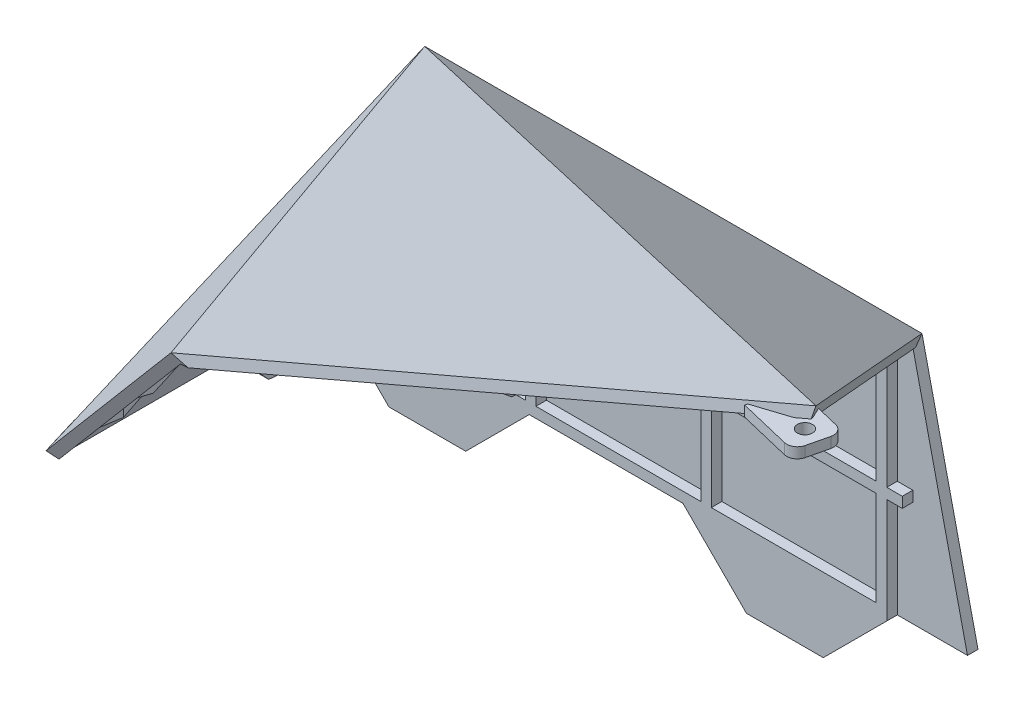
SolidWorks part; units mm, degrees
ref_plane "前视基准面" through (0, 0, 0) normal (0, 0, 1) x (1, 0, 0)
ref_plane "上视基准面" through (0, 0, 0) normal (0, 1, 0) x (1, 0, 0)
ref_plane "右视基准面" through (0, 0, 0) normal (1, 0, 0) x (0, 0, -1)
sketch "Sketch1" plane through (0, 0, 0) normal (0, 0, 1) x (1, 0, 0)
  line L0 (-295, -10) -> (-113.1586, -10)
  line L1 (-295, -10) -> (295, -10) construction
  line L2 (-113.1586, -10) -> (-129.1191, 60)
  line L3 (-129.1191, 60) -> (-270.8573, 60)
  line L4 (-270.8573, 60) -> (-295, -10)
  line L5 (-55, -10) -> (-295, -10) construction
  dimension "D1" = 70
extrude "Extrude1" add sketch "Sketch1" against normal blind 3
sketch "Sketch2" plane through (-260.5569, 89.8651, 0) normal (-0.9454, 0.326, 0) x (0, 0, 1)
  line L0 (0, -31.5915) -> (0, -105.6379)
  line L1 (0, -31.5915) -> (0, -105.6379) construction
  line L2 (0, -105.6379) -> (80.7874, -105.6379)
  line L5 (0, -31.5915) -> (80.7874, -105.6379)
extrude "Extrude2" add sketch "Sketch2" against normal blind 3
ref_plane "Plane1" through (0, 90, 0) normal (0, -1, 0) x (-1, 0, 0)
sketch "Sketch3" plane through (0, 90, 0) normal (0, -1, 0) x (-1, 0, 0)
  line L0 (201.3797, -153.6318) -> (201.3797, -124.7992) construction
  line L2 (226.9384, -143.7928) -> (224.0406, -143.7928) construction
  point P4 (201.3797, -138.7928)
  dimension "D1" = 5
ref_plane "Plane4" through (0, 120, 0) normal (0, 1, 0) x (1, 0, 0)
sketch "Sketch6" plane through (0, 120, 0) normal (0, 1, 0) x (1, 0, 0)
  point P0 (-66.3616, -89.9707)
ref_plane "Plane5" through (0, 43.7249, -28.2185) normal (0, 0.8402, -0.5422) x (1, 0, 0)
sketch "Sketch7" plane through (0, 43.7249, -28.2185) normal (0, 0.8402, -0.5422) x (1, 0, 0)
  line L0 (-66.3616, -140.6648) -> (-129.1191, -30.0142)
  line L1 (-129.1191, -30.0142) -> (-270.8573, -30.0142)
  line L2 (-270.8573, -30.0142) -> (-66.3616, -140.6648)
extrude "Extrude4" add sketch "Sketch7" against normal blind 3
ref_axis "Axis1" through (-270.8573, 60, -3) along (-0.2159, -0.626, 0.7493)
ref_plane "Plane6" through (-189.0801, 140.5222, 62.9169) normal (-0.7754, 0.5763, 0.258) x (0.214, -0.1446, 0.9661)
sketch "Sketch8" plane through (-189.0801, 140.5222, 62.9169) normal (-0.7754, 0.5763, 0.258) x (0.214, -0.1446, 0.9661)
  line L0 (77.9736, -48.7959) -> (-69.5404, -112.6077)
  line L1 (-69.5404, -112.6077) -> (16.3577, -184.1948)
  line L2 (16.3577, -184.1948) -> (77.9736, -48.7959)
extrude "Extrude5" add sketch "Sketch8" against normal blind 3
ref_plane "Plane7" through (-30.5316, 120.3261, -10.4979) normal (-0.2451, 0.9658, -0.0843) x (0.9695, 0.2441, -0.0213)
sketch "Sketch9" plane through (-30.5316, 120.3261, -10.4979) normal (-0.2451, 0.9658, -0.0843) x (0.9695, 0.2441, -0.0213)
  line L0 (-36.9571, -100.06) -> (-176.222, -146.0899)
  line L1 (-176.222, -146.0899) -> (-247.8849, -2.2263)
  line L2 (-247.8849, -2.2263) -> (-36.9571, -100.06)
extrude "Extrude6" add sketch "Sketch9" against normal blind 3
sketch "Sketch10" plane through (-189.0801, 140.5222, 62.9169) normal (-0.7754, 0.5763, 0.258) x (0.2124, -0.1468, 0.9661)
  line L1 (-95.6876, -88.5386) -> (16.8839, -88.5386)
  line L2 (-95.6876, -88.5386) -> (-95.6876, -178.6946)
  line L3 (-95.6876, -178.6946) -> (16.8839, -178.6946)
  line L4 (16.8839, -88.5386) -> (16.8839, -178.6946)
extrude "Extrude7" cut sketch "Sketch10" along normal blind 3
sketch "Sketch11" plane through (0, 0, -3) normal (0, 0, -1) x (-1, 0, 0)
  line L1 (239.3397, 70.1877) -> (313.0975, 70.1877)
  line L2 (239.3397, 70.1877) -> (239.3397, 55.4282)
  line L3 (239.3397, 55.4282) -> (313.0975, 55.4282)
  line L4 (313.0975, 70.1877) -> (313.0975, 55.4282)
extrude "Extrude8" cut sketch "Sketch11" along normal blind 3
sketch "Sketch12" plane through (0, -10, 0) normal (0, -1, 0) x (1, 0, 0)
  line L1 (-355.8844, -24.4832) -> (-188.0129, -24.4832)
  line L2 (-355.8844, -24.4832) -> (-355.8844, 171.382)
  line L3 (-355.8844, 171.382) -> (-188.0129, 171.382)
  line L4 (-188.0129, -24.4832) -> (-188.0129, 171.382)
extrude "Extrude10" cut sketch "Sketch12" along normal blind 3
sketch "Sketch13" plane through (-4.674, -42.3769, 80.6006) normal (-0.0513, -0.4648, 0.884) x (0.9987, -0.0281, 0.0431)
  line L1 (-217.8128, 155.7733) -> (-173.2445, 155.7733)
  line L2 (-217.8128, 155.7733) -> (-217.8128, 131.2611)
  line L3 (-217.8128, 131.2611) -> (-173.2445, 131.2611)
  line L4 (-173.2445, 155.7733) -> (-173.2445, 131.2611)
extrude "Extrude11" cut sketch "Sketch13" along normal blind 3
sketch "Sketch14" plane through (25.3769, 13.2736, 78.3364) normal (0.3043, 0.1591, 0.9392) x (0.9526, -0.0508, -0.3)
  line L1 (-122.9735, 108.9795) -> (-62.7635, 108.9795)
  line L2 (-122.9735, 108.9795) -> (-122.9735, 92.9613)
  line L3 (-122.9735, 92.9613) -> (-62.7635, 92.9613)
  line L4 (-62.7635, 108.9795) -> (-62.7635, 92.9613)
extrude "Extrude12" cut sketch "Sketch14" along normal blind 3
sketch "Sketch15" plane through (-110.5731, 34.0063, 52.6931) normal (0.8698, -0.2675, -0.4145) x (-0.3962, 0.1219, -0.91)
  line L1 (-45.3554, 87.1221) -> (-30.4661, 87.1221)
  line L2 (-45.3554, 87.1221) -> (-45.3554, 100.6095)
  line L3 (-45.3554, 100.6095) -> (-30.4661, 100.6095)
  line L4 (-30.4661, 87.1221) -> (-30.4661, 100.6095)
extrude "Extrude13" cut sketch "Sketch15" along normal blind 3
ref_plane "Plane8" through (-113.1586, 0, 0) normal (1, 0, 0) x (0, 0, 1)
ref_plane "Plane9" through (-133.1586, 0, 0) normal (1, 0, 0) x (0, 0, 1)
sketch "Sketch16" plane through (-133.1586, 0, 0) normal (1, 0, 0) x (0, 0, 1)
  line L0 (0, 10) -> (3, 10)
  line L1 (0, 10) -> (78.6977, 10) construction
  line L2 (3, 10) -> (3, -56.3954)
  line L3 (3, -56.3954) -> (61.3359, -94.6114)
  line L5 (60.3255, -97.5359) -> (0, -58.0165)
  line L6 (0, -58.0165) -> (0, 10)
  line L7 (61.3359, -94.6114) -> (109.8837, -98.7641)
  line L8 (109.8837, -98.7641) -> (113.968, -102.1244)
  line L9 (113.968, -102.1244) -> (60.3255, -97.5359)
  dimension "D1" = 3
  dimension "D2" = 3
  dimension "D3" = 3
extrude "Extrude14" add sketch "Sketch16" against normal blind 3
ref_plane "Plane10" through (-183.1586, 0, 0) normal (1, 0, 0) x (0, 0, 1)
sketch "Sketch17" plane through (-183.1586, 0, 0) normal (1, 0, 0) x (0, 0, 1)
  line L0 (0, 10) -> (3, 10)
  line L1 (3, 10) -> (3, -56.794)
  line L2 (3, -56.794) -> (38.6933, -79.8309)
  line L3 (38.6933, -79.8309) -> (129.1337, -87.6954)
  line L4 (129.1337, -87.6954) -> (132.2454, -90.9773)
  line L5 (132.2454, -90.9773) -> (37.6918, -82.7551)
  line L6 (37.6918, -82.7551) -> (0, -58.4283)
  line L7 (0, -58.4283) -> (0, 10)
  dimension "D1" = 3
  dimension "D2" = 3
extrude "Extrude15" add sketch "Sketch17" against normal blind 3
ref_plane "Plane11" through (-233.1586, 0, 0) normal (1, 0, 0) x (0, 0, 1)
sketch "Sketch18" plane through (-233.1586, 0, 0) normal (1, 0, 0) x (0, 0, 1)
  line L0 (0, 10) -> (3, 10)
  line L1 (3, 10) -> (3, -56.7705)
  line L2 (3, -56.7705) -> (15.9753, -65.1599)
  line L3 (15.9753, -65.1599) -> (69.5504, -69.8189)
  line L4 (69.5504, -69.8189) -> (112.0526, -50.7804)
  line L5 (112.0526, -50.7804) -> (116.7786, -51.9506)
  line L6 (116.7786, -51.9506) -> (70.0662, -72.8751)
  line L7 (70.0662, -72.8751) -> (14.9726, -68.084)
  line L8 (14.9726, -68.084) -> (0, -58.4033)
  line L9 (0, -58.4033) -> (0, 10)
  dimension "D1" = 3
  dimension "D2" = 3
  dimension "D3" = 3
extrude "Extrude16" add sketch "Sketch18" against normal blind 3
sketch "Sketch19" plane through (-133.1586, 0, 0) normal (1, 0, 0) x (0, 0, -1)
  line L1 (18.1, -7) -> (-3, -7)
  line L2 (18.1, -7) -> (18.1, -28.1)
  line L3 (18.1, -28.1) -> (-3, -28.1)
  line L4 (-3, -7) -> (-3, -28.1)
  line L5 (15.1, -10) -> (0, -10)
  line L6 (15.1, -10) -> (15.1, -25.1)
  line L7 (15.1, -25.1) -> (0, -25.1)
  line L8 (0, -10) -> (0, -25.1)
  line L9 (0, -10) -> (0, 58.3656) construction
  dimension "D1" = 15.1
  dimension "D2" = 15.1
  dimension "D3" = 3
  dimension "D4" = 3
  dimension "D5" = 3
  dimension "D6" = 3
extrude "Extrude17" add sketch "Sketch19" against normal blind 160
sketch "Sketch20" plane through (0, 0, -18.1) normal (0, 0, -1) x (-1, 0, 0)
  line L0 (173.1586, -28.1) -> (191.2586, -10)
  line L1 (293.1586, -28.1) -> (133.1586, -28.1) construction
  line L2 (191.2586, -10) -> (235.0586, -10)
  line L3 (235.0586, -10) -> (253.1586, -28.1)
  line L4 (253.1586, -28.1) -> (173.1586, -28.1)
  line L5 (133.1586, -10) -> (113.1586, -10) construction
  line L6 (133.1586, -28.1) -> (133.1586, -7) construction
  line L7 (293.1586, -28.1) -> (293.1586, -7) construction
  line L8 (133.1586, -10) -> (151.2586, -28.1)
  line L9 (151.2586, -28.1) -> (133.1586, -28.1)
  line L10 (133.1586, -28.1) -> (133.1586, -10)
  line L11 (293.1586, -10) -> (275.0586, -28.1)
  line L12 (275.0586, -28.1) -> (293.1586, -28.1)
  line L13 (293.1586, -28.1) -> (293.1586, -10)
  dimension "D1" = 45
  dimension "D2" = 45
  dimension "D3" = 40
  dimension "D4" = 40
extrude "Extrude18" cut sketch "Sketch20" against normal blind 160
sketch "Sketch21" plane through (0, -28.1, 0) normal (0, -1, 0) x (1, 0, 0)
  line L0 (-264.1086, 3) -> (-264.1086, -18.1) construction
  line L1 (-275.0586, 3) -> (-253.1586, 3) construction
  line L2 (-275.0586, -18.1) -> (-253.1586, -18.1) construction
  line L3 (-162.2086, 3) -> (-162.2086, -18.1) construction
  line L4 (-173.1586, 3) -> (-151.2586, 3) construction
  line L5 (-173.1586, -18.1) -> (-151.2586, -18.1) construction
  line L6 (-275.0586, -7.55) -> (-151.2586, -7.55) construction
  line L7 (-275.0586, 3) -> (-275.0586, -18.1) construction
  line L8 (-151.2586, 3) -> (-151.2586, -18.1) construction
  circle A0 centre (-264.1086, -7.55) radius 1.7
  circle A1 centre (-162.2086, -7.55) radius 1.7
  dimension "D1" = 3.4
extrude "Extrude19" cut sketch "Sketch21" against normal blind 10
ref_plane "Plane12" through (0, 20, 0) normal (0, -1, 0) x (-1, 0, 0)
sketch "Sketch22" plane through (0, 20, 0) normal (0, -1, 0) x (-1, 0, 0)
  line L0 (128.7465, 0) -> (128.7465, -3)
  line L1 (128.7465, -3) -> (278.5019, -3)
  line L2 (278.5019, -3) -> (278.5019, -43.0666)
  line L3 (278.5019, -43.0666) -> (262.1738, -91.5327)
  line L4 (262.1738, -91.5327) -> (263.2164, -97.8345)
  line L5 (263.2164, -97.8345) -> (281.5019, -43.5584)
  line L6 (281.5019, -43.5584) -> (281.5019, 0)
  line L8 (281.5019, 0) -> (128.7465, 0)
  dimension "D1" = 3
  dimension "D2" = 3
  dimension "D3" = 3
extrude "Extrude20" add sketch "Sketch22" against normal blind 3
ref_plane "Plane13" through (0, 113, 0) normal (0, -1, 0) x (-1, 0, 0)
sketch "Sketch23" plane through (0, 113, 0) normal (0, -1, 0) x (-1, 0, 0)
  line L0 (77.9028, -84.1926) -> (80.7274, -95.9325)
  line L1 (77.9028, -84.1926) -> (60, -88.5)
  line L2 (80.7274, -95.9325) -> (62.8246, -100.2399)
  line L3 (60, -88.5) -> (62.8246, -100.2399)
  point P0 (83.5609, -95.0761)
extrude "Extrude21" add sketch "Sketch23" against normal blind 3
fillet "Fillet1" radius 3 2 edges at (-62.8246, 114.5, 100.2399) (-60, 114.5, 88.5)
sketch "Sketch26" plane through (0, 116, 0) normal (0, 1, 0) x (1, 0, 0)
  line L0 (-60.7018, -91.4168) -> (-62.1228, -97.3231) construction
  line L1 (-61.4123, -94.3699) -> (-66.2736, -93.2003) construction
  circle A0 centre (-66.2736, -93.2003) radius 2.15
  dimension "D1" = 5
  dimension "D2" = 4.3
extrude "Extrude25" cut sketch "Sketch26" against normal blind 3
